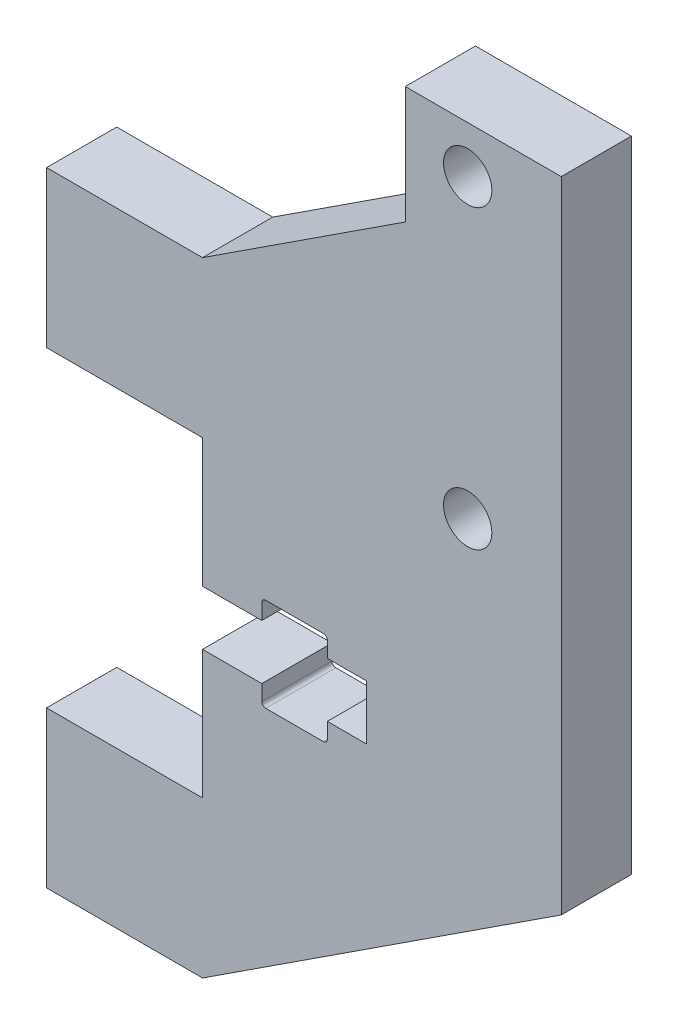
SolidWorks part; units mm, degrees
ref_plane "Front Plane" through (0, 0, 0) normal (0, 0, 1) x (1, 0, 0)
ref_plane "Top Plane" through (0, 0, 0) normal (0, 1, 0) x (1, 0, 0)
ref_plane "Right Plane" through (0, 0, 0) normal (1, 0, 0) x (0, 0, -1)
sketch "Sketch1" plane through (0, 0, 0) normal (0, 0, 1) x (1, 0, 0)
  line L0 (13, 3.4783) -> (0, -5)
  line L1 (0, -5) -> (-10, -5)
  line L2 (-10, -5) -> (-10, -15)
  line L3 (-10, -15) -> (0, -15)
  line L4 (0, -15) -> (0, -35)
  line L5 (0, -35) -> (-10, -35)
  line L6 (-10, -35) -> (-10, -45)
  line L7 (-10, -45) -> (0, -45)
  line L10 (0, -45) -> (23, -30)
  line L11 (23, -30) -> (23, 11)
  line L12 (23, 11) -> (13, 11)
  line L13 (13, 11) -> (13, 3.4783)
  line L15 (0, -5) -> (0, -45) construction
  line L16 (-10, -10) -> (0, -10) construction
  line L17 (-10, -40) -> (0, -40) construction
  line L18 (-10, -15) -> (-10, -35) construction
  line L19 (-10, -25) -> (0, -25) construction
  dimension "D2" = 10
  dimension "D3" = 10
  dimension "D4" = 10
  dimension "D5" = 15
  dimension "D8" = 10
  dimension "D10" = 13
  dimension "D6" = 15
  dimension "D7" = 16
extrude "Boss-Extrude1" add sketch "Sketch1" along normal blind 4.5
sketch "Sketch2" plane through (0, 0, 4.5) normal (0, 0, 1) x (1, 0, 0)
  line L0 (0, -25) -> (23, -25) construction
  line L1 (0, -15) -> (0, -35) construction
  line L3 (10.5, -26.75) -> (10.5, -23.25) construction
  line L4 (10.5, -23.25) -> (0, -23.25) construction
  line L5 (0, -26.75) -> (0, -23.25)
  line L6 (0, -23.25) -> (3.8, -23.25)
  line L7 (3.8, -23.25) -> (3.8, -22.25)
  line L8 (4.05, -22) -> (7.75, -22)
  line L9 (8, -22.25) -> (8, -23.25)
  line L10 (8, -23.25) -> (10.5, -23.25)
  line L11 (10.5, -23.25) -> (10.5, -26.75)
  line L12 (10.5, -26.75) -> (0, -26.75) construction
  line L13 (8, -26.75) -> (10.5, -26.75)
  line L14 (8, -27.75) -> (8, -26.75)
  line L15 (4.05, -28) -> (7.75, -28)
  line L16 (3.8, -26.75) -> (3.8, -27.75)
  line L17 (0, -26.75) -> (3.8, -26.75)
  line L18 (23, -30) -> (23, 11) construction
  arc A0 (7.75, -22) -> (8, -22.25) centre (7.75, -22.25) cw
  arc A1 (3.8, -22.25) -> (4.05, -22) centre (4.05, -22.25) cw
  arc A2 (3.8, -27.75) -> (4.05, -28) centre (4.05, -27.75) ccw
  arc A3 (7.75, -28) -> (8, -27.75) centre (7.75, -27.75) ccw
  point P15 (8, -22)
  point P18 (3.8, -22)
  point P27 (10.5, -25)
  point P29 (3.8, -28)
  point P30 (8, -28)
  dimension "D6" = 0.25
  dimension "D1" = 10.5
  dimension "D2" = 1.75
  dimension "D3" = 8
  dimension "D4" = 4.2
  dimension "D5" = 3
extrude "screw-cutout" cut sketch "Sketch2" against normal through all
sketch "Sketch3" plane through (0, 0, 4.5) normal (0, 0, 1) x (1, 0, 0)
  line L0 (17, 55) -> (17, -45) construction
  line L3 (13, 11) -> (13, 3.4783) construction
  line L5 (-10, -45) -> (0, -45) construction
  line L10 (10.5, -26.75) -> (10.5, -23.25) construction
  circle A1 centre (17, 8) radius 1.55
  circle A5 centre (17, -11) radius 1.55
  point P8 (10.5, -25)
  dimension "D4" = 3.1
  dimension "D11" = 3.1
  dimension "D6" = 4
  dimension "D12" = 19
  dimension "D2" = 14
extrude "Cut-Extrude2" cut sketch "Sketch3" against normal through all
sketch "Sketch4" plane through (0, 0, 4.5) normal (0, 0, 1) x (1, 0, 0)
  line L0 (17, -11) -> (17, 8) construction
  line L1 (17, -1.5) -> (13, -1.5) construction
  line L2 (13, 11) -> (13, 3.4783) construction
  line L4 (15, 2.5) -> (13, 2.5)
  line L5 (15, 2.5) -> (15, -5.5)
  line L6 (15, -5.5) -> (13, -5.5)
  line L7 (13, 2.5) -> (13, -5.5)
  line L8 (15, 2.5) -> (13, -5.5) construction
  line L9 (15, -5.5) -> (13, 2.5) construction
  circle A1 centre (17, 8) radius 1.55 construction
  circle A3 centre (17, -11) radius 1.55 construction
  point P11 (14, -1.5)
  dimension "D1" = 8
  dimension "D2" = 2
  dimension "D3" = 3
equation "\"X-ROD-SPACING\"=45"
equation "\"Y-ROD-SPACING\"=75"
equation "\"Z-ROD-SPACING\"=17.5"
equation "\"Y-BED-OFFSET\"=2"
equation "\"Y-BED-ROD-INSET\"=3.5"
equation "\"T-SLOT-NUT-FILLET-RADIUS\"=0.25"
equation "\"T-SLOT-SCREW-SHAFT-RADIUS\"=1.75"
equation "\"T-SLOT-SCREW-SHAFT-CUTOUT-LENGTH\"=10.5"
equation "\"T-SLOT-NUT-DEPTH\"=4.2"
equation "\"T-SLOT-NUT-WIDTH\"=3"
equation "\"T-SLOT-NUT-END-DISTANCE\"=8"
equation "\"ACRYLIC-THICKNESS\"=10"
equation "\"ACRYLIC-THICKNESS2\"=4.5"
equation "\"ACRYLIC-TAB-CUTOUT-SIZE\"=\"ACRYLIC-THICKNESS\"+\"ACRYLIC-TAB-TOLERANCE\"*2"
equation "\"ACRYLIC-TAB-WIDTH\"=\"ACRYLIC-THICKNESS\""
equation "\"ACRYLIC-M3-HOLE\"=3.1"
equation "\"SMOOTHROD-CAP-SCREW-DISTANCE\"=20"
equation "\"FRAME-WIDTH-INNER\"=370"
equation "\"NEMA17-HOLE-SPACING\"=31"
equation "\"NEMA17-CENTRAL-CUTOUT\"=22.5"
equation "\"Z-BRACKET-REACH\"=55"
equation "\"Z-ROD-INSET\"=16"
equation "\"TOP-BRACKET-SPACING\"=40"
equation "\"SMOOTHROD-X-LENGTH\"=350"
equation "\"SMOOTHROD-Y-LENGTH\"=350"
equation "\"SMOOTHROD-Z-LENGTH\"=350"
equation "\"SMOOTHROD-TIGHTENING-HEADROOM\"=.25"
equation "\"LEADSCREW-Z-LENGTH\"=300"
equation "\"SCREW-LENGTH-FRAME\"=\"ACRYLIC-THICKNESS\" + 10"
equation "\"SCREW-HEAD-RADIUS\"=6"
equation "\"PRINTED-X-SMOOTHROD-DIAMETER\"=8.2"
equation "\"PRINTED-X-SMOOTHROD-CUTOUT\"=10"
equation "\"PRINTED-X-BASE-HEIGHT\"=10"
equation "\"PRINTED-LM8UU-CUTOUT-SIZE\"=15.25"
equation "\"PRINTED-LM8UU-CUTOUT-LENGTH\"=24.5"
equation "\"PRINTED-X-IDLER-HEIGHT\"=16"
equation "\"PSU-MOUNTING-WIDTH\"=95"
equation "\"PSU-MOUNTING-HEIGHT\"=177"
equation "\"Y-BELT-TO-ROD-DISTANCE\"=20"
equation "\"SPOOL-HOLDER-ROD-SPACING\"=150"
equation "\"D1@Sketch1\"=\"ACRYLIC-TAB-WIDTH\""
equation "\"D2@Sketch1\"=\"ACRYLIC-TAB-WIDTH\""
equation "\"D3@Sketch1\"=\"ACRYLIC-THICKNESS\""
equation "\"D4@Sketch1\"=\"ACRYLIC-THICKNESS\""
equation "\"D1@Boss-Extrude1\"=\"ACRYLIC-THICKNESS2\""
equation "\"D1@Sketch2\"=\"T-SLOT-SCREW-SHAFT-CUTOUT-LENGTH\""
equation "\"D2@Sketch2\"=\"T-SLOT-SCREW-SHAFT-RADIUS\""
equation "\"D3@Sketch2\"=\"T-SLOT-NUT-END-DISTANCE\""
equation "\"D4@Sketch2\"=\"T-SLOT-NUT-DEPTH\""
equation "\"D5@Sketch2\"=\"T-SLOT-NUT-WIDTH\""
equation "\"D6@Sketch2\"=\"T-SLOT-NUT-FILLET-RADIUS\""
equation "\"D4@Sketch3\"=\"ACRYLIC-M3-HOLE\""
equation "\"D11@Sketch3\"=\"ACRYLIC-M3-HOLE\""
equation "\"Y-BED-SCREW-SPACING\"=209"
equation "\"Y-BED-SCREW-CUTOUT-SLOT-HEIGHT\"=2"
equation "\"ACRYLIC-TAB-TOLERANCE\"=.1"
equation "\"SCREW-LENGTH-MOTOR\"=\"ACRYLIC-THICKNESS\" + 5"
equation "\"SCREW-LENGTH-EXTRUDER\"=28"
equation "\"PRINTED-M3-HOLE\"=3.5"
equation "\"ACRYLIC-X-CARRIAGE-WIDTH\"=55"
equation "\"ACRYLIC-X-CARRIAGE-HEIGHT\"=75"
equation "\"ACRYLIC-X-CARRIAGE-LM8UU-CUTOUT-WIDTH\"=24.25"
equation "\"ACRYLIC-X-CARRIAGE-LM8UU-CUTOUT-HEIGHT\"=11.5"
equation "\"ACRYLIC-X-CARRIAGE-SCREW-SPACING-X\"=15"
equation "\"ACRYLIC-X-CARRIAGE-SCREW-SPACING-Y\"=33"
equation "\"ACRYLIC-X-CARRIAGE-CENTER-TAB-SPACING\"=14"
equation "\"ACRYLIC-X-CARRIAGE-EXTRUDER-OFFSET\"=26"
equation "\"ACRYLIC-X-CARRIAGE-EXTRUDER-ANGLE\"=90"
equation "\"ACRYLIC-X-CARRIAGE-EXTRUDER-SHELF-DEPTH\"=\"ACRYLIC-X-CARRIAGE-EXTRUDER-OFFSET\" + 28"
equation "\"ACRYLIC-X-CARRIAGE-EXTRUDER-BRACE-SPACING\"=23"
equation "\"ACRYLIC-X-CARRIAGE-EXTRUDER-BRACE-TAB-OFFSET\"=20"
equation "\"ACRYLIC-X-CARRIAGE-EXTRUDER-BRACE-HEIGHT\"=35"
equation "\"ACRYLIC-X-CARRIAGE-EXTRUDER-BRACE-SCREW-SPACING\"=22"
equation "\"ACRYLIC-X-CARRIAGE-DUAL-WIDTH-MULTIPLIER\"=1.65"
equation "\"ACRYLIC-X-CARRIAGE-DUAL-HOTEND-SPACING\"=42"
equation "\"ACRYLIC-X-CARRIAGE-DUAL-WIDTH\"=103"
equation "\"ACRYLIC-X-CARRIAGE-DUAL-HOTEND-SEPARATION\"=35"
equation "\"ACRYLIC-X-CARRIAGE-DUAL-MOUNT-PLATE-DEPTH\"=76"
equation "\"ACRYLIC-X-CARRIAGE-DUAL-MOUNT-BRACE-WIDTH\"=45"
equation "\"ACRYLIC-X-CARRIAGE-DUAL-MOUNT-SCREW-WIDTH\"=40"
equation "\"BLOWER-FAN-WIDTH\"=15"
